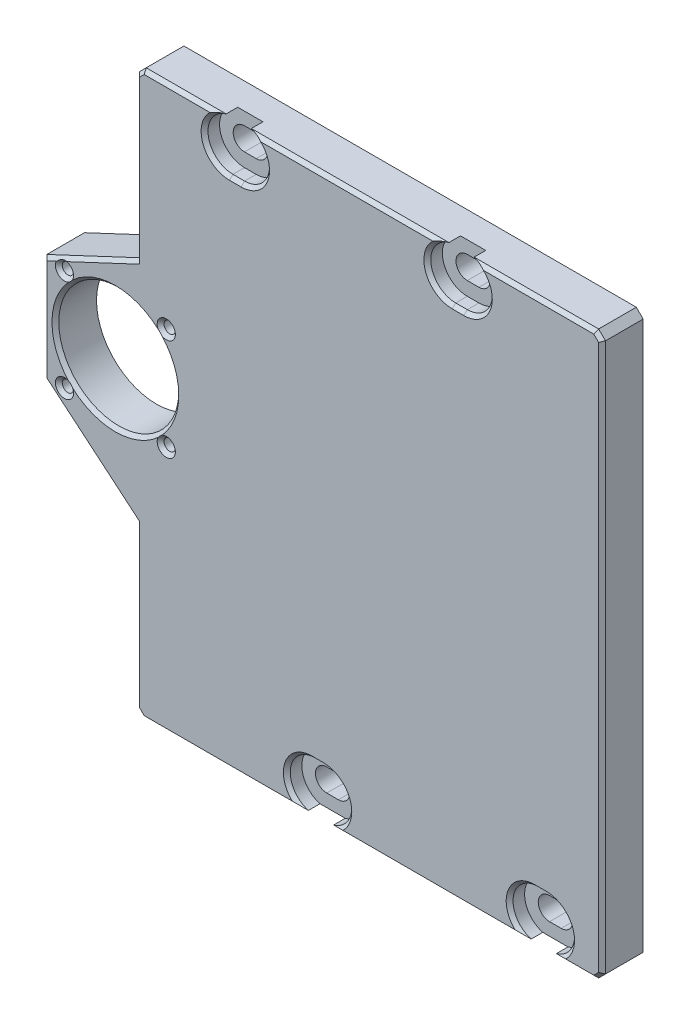
SolidWorks part; units mm, degrees
ref_plane "Front Plane" through (0, 0, 0) normal (0, 0, 1) x (1, 0, 0)
ref_plane "Top Plane" through (0, 0, 0) normal (0, 1, 0) x (1, 0, 0)
ref_plane "Right Plane" through (0, 0, 0) normal (1, 0, 0) x (0, 0, -1)
sketch "Sketch1" plane through (0, 0, 0) normal (0, 0, 1) x (1, 0, 0)
  line L0 (-24, 207) -> (-12, 207)
  line L1 (-148, 207) -> (-24, 207)
  line L3 (-148, 43) -> (-24, 43)
  line L4 (-12, 207) -> (-12, 43)
  line L6 (-175, 145.3297) -> (-175, 114.6703) construction
  line L9 (-175, 145.3297) -> (-175, 114.6703)
  line L12 (-24, 43) -> (-12, 43)
  line L18 (-148, 62) -> (-148, 92)
  line L19 (-148, 43) -> (-148, 57)
  line L20 (-148, 57) -> (-148, 62)
  line L23 (-148, 207) -> (-148, 193)
  line L25 (-148, 193) -> (-148, 188)
  line L27 (-148, 188) -> (-148, 158)
  line L29 (-148, 158) -> (-175, 145.3297)
  line L30 (-175, 114.6703) -> (-148, 92)
  circle A30 centre (-154, 130) radius 17.5
  circle A31 centre (-154, 130) radius 17.5
  dimension "D3" = 0.5
extrude "Boss-Extrude1" add sketch "Sketch1" along normal blind 12
sketch "Sketch2" plane through (0, 0, 12) normal (0, 0, 1) x (1, 0, 0)
  line L6 (-148, 207) -> (-148, 158)
  line L7 (-175, 145.3297) -> (-175, 114.6703)
  line L9 (-148, 43) -> (-12, 43)
  line L10 (-12, 43) -> (-12, 207)
  line L11 (-12, 207) -> (-148, 207)
  line L13 (-175, 145.3297) -> (-175, 114.6703)
  line L15 (-148, 43) -> (-12, 43)
  line L16 (-12, 43) -> (-12, 207)
  line L17 (-12, 207) -> (-148, 207)
  line L20 (-148, 207) -> (-148, 158)
  line L22 (-148, 158) -> (-175, 145.3297)
  line L28 (-148, 92) -> (-148, 43)
  line L29 (-148, 92) -> (-148, 43)
  line L30 (-148, 158) -> (-175, 145.3297)
  line L32 (-175, 114.6703) -> (-148, 92)
  line L33 (-175, 114.6703) -> (-148, 92)
  circle A0 centre (-139.1508, 115.1508) radius 2.25 construction
  circle A1 centre (-139.1508, 115.1508) radius 2.25
  circle A2 centre (-168.8492, 115.1508) radius 2.25 construction
  circle A3 centre (-168.8492, 115.1508) radius 2.25
  circle A4 centre (-168.8492, 144.8492) radius 2.25 construction
  circle A5 centre (-168.8492, 144.8492) radius 2.25
  circle A6 centre (-139.1508, 144.8492) radius 2.25 construction
  circle A7 centre (-139.1508, 144.8492) radius 2.25
  dimension "D1" = 0
hole_wizard "M4x0.7 Tapped Hole1" positions "Sketch3" profile "Sketch4" tap size "M4x0.7" standard "ANSI Metric"
sketch "Sketch3" plane through (0, 0, 12) normal (0, 0, 1) x (1, 0, 0)
  point P0 (-168.8492, 144.8492)
  point P3 (-139.1508, 144.8492)
  point P6 (-139.1508, 115.1508)
  point P9 (-168.8492, 115.1508)
sketch "Sketch4" plane through (-168.8492, 144.8492, 12) normal (1, 0, 0) x (0, -1, 0)
  line L0 (0, 0) -> (0, 14.1)
  line L1 (0, 14.1) -> (1.65, 13.1086)
  line L2 (1.65, 13.1086) -> (1.65, 0)
  line L5 (1.65, 0) -> (0, 0)
  line L10 (0, 14.1) -> (-1.65, 13.1086) construction
  line L11 (0, -6.35) -> (0, 107.95) construction
  dimension "Tap Drill Dia." = 3.3
  dimension "Tap Drill Depth" = 14.1
  dimension "Drill Angle" = 118
cosmetic thread "Hole Thread1" parameters "D1"=12, "D2"=4
cosmetic thread "Hole Thread2" parameters "D1"=12, "D2"=4
cosmetic thread "Hole Thread3" parameters "D1"=12, "D2"=4
cosmetic thread "Hole Thread4" parameters "D1"=12, "D2"=4
chamfer "Chamfer1" distance 2 angle 45 4 edges at (-12, 43, 6) (-148, 43, 6) (-12, 207, 6) (-148, 207, 6)
sketch "Sketch7" plane through (0, 0, 12) normal (0, 0, 1) x (1, 0, 0)
  line L0 (-48, 200) -> (-54, 200) construction
  line L1 (-148, 200) -> (-119, 200) construction
  line L2 (-48, 200) -> (-54, 200)
  line L3 (-148, 200) -> (-119, 200)
  line L4 (0, 50) -> (-30, 50) construction
  line L5 (-125, 50) -> (-95, 50) construction
  line L6 (0, 50) -> (-30, 50)
  line L7 (-125, 50) -> (-95, 50)
hole_wizard "CBORE SLOT for M6 Hex Head Bolt1" positions "Sketch10" profile "Sketch11" size "M6" standard "ANSI Metric" slot yes
sketch "Sketch10" plane through (0, 0, 12) normal (0, 0, 1) x (1, 0, 0)
  line L0 (-114, 200) -> (-124, 200) construction
  point P0 (-119, 200)
  point P5 (-54, 200)
  point P8 (-30, 50)
  point P11 (-95, 50)
  dimension "D1" = 10
sketch "Sketch11" plane through (-119, 200, 12) normal (1, 0, 0) x (0, -1, 0)
  line L0 (0, 0) -> (0, 23)
  line L1 (0, 23) -> (3.3, 21.0172)
  line L2 (3.3, 21.0172) -> (3.3, 4.38)
  line L3 (3.3, 4.38) -> (7.275, 4.38)
  line L4 (7.275, 4.38) -> (7.275, 0)
  line L5 (7.275, 0) -> (0, 0)
  line L10 (0, 23) -> (-3.3, 21.0172) construction
  line L11 (0, -6.35) -> (0, 107.95) construction
  dimension "Hole Dia." = 6.6
  dimension "Hole Depth" = 23
  dimension "C'Bore Dia." = 14.55
  dimension "C'Bore Depth" = 4.38
  dimension "Drill Angle" = 118
chamfer "Chamfer2" distance 1 angle 45 33 edges at (-136.5, 130, 12) (-167.1992, 115.1508, 12) (-137.5008, 115.1508, 12) (-137.5008, 144.8492, 12) (-167.1992, 144.8492, 12) (-45.0941, 198.9998, 12) (-62.9059, 198.9998, 12) (-32.1593, 207, 12) (-13, 206, 12) (-12, 125, 12) (-13, 44, 12) (-20.1593, 43, 12) (-38.9059, 51.0002, 12) (-21.0941, 51.0002, 12) (-103.9059, 51.0002, 12) (-86.0941, 51.0002, 12) (-122.3407, 43, 12) (-147, 44, 12) (-148, 68.5, 12) (-175, 130, 12) (-148, 181.5, 12) (-147, 206, 12) (-134.3407, 207, 12) (-110.0941, 198.9998, 12) (-127.9059, 198.9998, 12) (-86.5, 207, 12) (-54, 192.725, 12) (-30, 57.275, 12) (-62.5, 43, 12) (-95, 57.275, 12) (-161.5, 103.3351, 12) (-161.5, 151.6649, 12) (-119, 192.725, 12)
